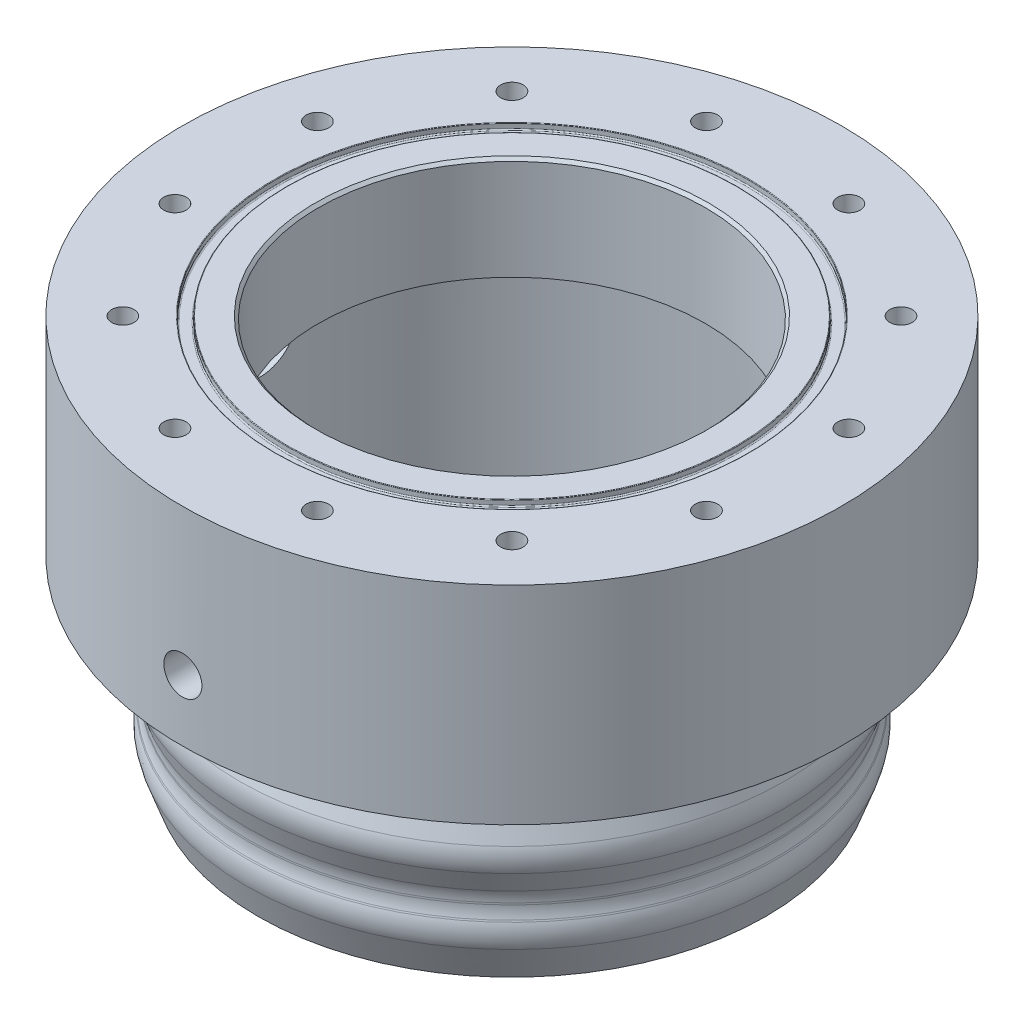
SolidWorks part; units mm, degrees
note: '?' marks a value the reader was unsure of.
material "7075-T6 (SN)"
ref_plane "Front Plane" through (0, 0, 0) normal (0, 0, 1) x (1, 0, 0)
ref_plane "Top Plane" through (0, 0, 0) normal (0, 1, 0) x (1, 0, 0)
ref_plane "Right Plane" through (0, 0, 0) normal (1, 0, 0) x (0, 0, -1)
sketch "Flange profile" plane through (0, 0, 0) normal (0, 0, 1) x (1, 0, 0)
  line L0 (0, 0) -> (0, 94.4875) construction
  line L1 (-42.8625, 22.86) -> (-42.8625, 0)
  line L2 (-73.025, 22.86) -> (-52.5653, 22.86)
  line L3 (-42.8625, 0) -> (-55.7276, 0)
  line L4 (-55.7276, 0) -> (-55.7276, -64.2669)
  line L5 (-42.8625, 22.86) -> (-49.7459, 22.86)
  line L6 (-52.4383, 22.733) -> (-52.4383, 21.7932)
  line L7 (-52.1843, 21.5392) -> (-50.1269, 21.5392)
  line L8 (-49.8729, 21.7932) -> (-49.8729, 22.733)
  line L9 (-73.025, 22.86) -> (-73.025, -23.1513)
  line L11 (-73.025, -23.1513) -> (-48.6828, -23.1513) construction
  line L16 (-58.2676, -47.2363) -> (-58.2676, -50.3097)
  line L17 (-73.025, -23.1513) -> (-58.2676, -23.1513)
  line L18 (-48.9204, -44.4628) -> (-48.9204, -68.3701) construction
  line L19 (-58.2676, -47.2363) -> (-61.3156, -38.862)
  line L20 (-61.3156, -38.862) -> (-58.2676, -30.4877)
  line L21 (-58.2676, -30.4877) -> (-58.2676, -23.1513)
  line L22 (-59.7916, -54.4969) -> (-56.2356, -64.2669)
  line L23 (-56.2356, -64.2669) -> (-55.7276, -64.2669)
  line L24 (-58.2676, -50.3097) -> (-59.7916, -54.4969)
  arc A0 (-49.8729, 21.7932) -> (-50.1269, 21.5392) centre (-50.1269, 21.7932) cw
  arc A1 (-52.1843, 21.5392) -> (-52.4383, 21.7932) centre (-52.1843, 21.7932) cw
  arc A2 (-49.7459, 22.86) -> (-49.8729, 22.733) centre (-49.7459, 22.733) ccw
  arc A3 (-52.4383, 22.733) -> (-52.5653, 22.86) centre (-52.5653, 22.733) ccw
  point P27 (-49.8729, 21.5392)
  point P32 (-49.8729, 22.86)
  point P35 (-52.4383, 22.86)
  dimension "D20" = 61.722
  dimension "D22" = 0.508
  dimension "D12" = 0.254
  dimension "D14" = 0.254
  dimension "D18" = 0.127
  dimension "D21" = 0.127
  dimension "D3" = 73.025
  dimension "D4" = 55.7276
  dimension "D5" = 4.064
  dimension "D6" = 52.4383
  dimension "D7" = 2.5654
  dimension "D8" = 1.3208
  dimension "D9" = 2.54
  dimension "D10" = 42.8625
  dimension "D11" = 20
  dimension "D13" = 2.54
  dimension "D15" = 20
  dimension "D16" = 46.0113
  dimension "D17" = 5.588
  dimension "D23" = 20
  dimension "D24" = 20
  dimension "D25" = 3.0734
revolve "Flange" add sketch "Flange profile" angle 360 about L0
ref_axis "center of part" through (0, 0, 0) along (0, -1, 0)?
ref_plane "Igniter Ref Plane" through (-71.0946, 0, 0) normal (1, 0, 0) x (0, 0, -1)
ref_plane "Assembly Bolt Offset Angle" through (0, 0, 0) normal (-0.2588, 0, 0.9659) x (0.9659, 0, 0.2588)
sketch "Assembly Bolt Insert Diameter" plane through (0, 22.86, 0) normal (0, 1, 0) x (1, 0, 0)
  line L0 (-70.4383, 18.8739) -> (70.4383, -18.8739) construction
  circle A0 centre (-58.8828, 15.7776) radius 2.4892
  dimension "D2" = 4.9784
  dimension "D1" = 60.96
extrude "Assembly Bolt Insert Cut" cut sketch "Assembly Bolt Insert Diameter" against normal blind 21.59
pattern_circular "Assembly Bolts" count 12 over 360 about axis through (0, 0, 0) along (0, 1, 0) of "Assembly Bolt Insert Cut"
sketch "Ref Line for Igniter Cut" plane through (0, 0, 0) normal (0, -1, 0) x (1, 0, 0)
  line L0 (-38.1, 0) -> (-38.1, 25.3157)
thread "Thread6" [suppressed] pitch 1.27 start angle 0, offset 0, length 20.32, pitch 1.27, diameter 4.9784
ref_plane "Plane9" through (-18.2668, 22.86, 58.8828) normal (0, 0, 1) x (-1, 0, 0)
sketch "Thread Profile7" plane through (-18.2668, 22.86, 58.8828) normal (0, 0, 1) x (-1, 0, 0)
  line L0 (0, 0) -> (0, 1.27) construction
  line L1 (0, 0) -> (0.6874, 0.3969)
  line L2 (0.6874, 0.3969) -> (0.6874, 0.5556)
  line L3 (0.6874, 0.5556) -> (0, 0.9525)
  line L4 (0.6874, 0.4762) -> (0, 0.4762) construction
  line L11 (0, 0) -> (0, 0.9525)
  point P2 (0, 0)
  dimension "Pitch" = 1.27
  dimension "Profile_Angle" = 60
  dimension "Profile_Land" = 0.1588
  dimension "Profile_Height" = 0.6874
ref_plane "Plane for Igniter Angle" through (-73.025, 0, 0) normal (-1, 0, 0) x (0, 0, 1)
sketch "Location and sizing of Igniter Cut and Boss" plane through (-73.025, 0, 0) normal (-1, 0, 0) x (0, 0, 1)
  line L5 (0, -55) -> (0, 55) construction
  circle A0 centre (0, 0) radius 8.7122
  dimension "D1" = 17.4244
ref_plane "Igniter Boss Plane" through (-81.3816, 0, 0) normal (1, 0, 0) x (0, 0, -1)
ref_plane "Plane for Pt Cut" through (0, 0, 50.8) normal (0, 0, 1) x (1, 0, 0)
sketch "Pt Cut Diameter" plane through (0, 0, 50.8) normal (0, 0, 1) x (1, 0, 0)
  circle A0 centre (0, -9.525) radius 4.2164
  dimension "D1" = 9.525
  dimension "D2" = 8.4328
extrude "Pt Cut" cut sketch "Pt Cut Diameter" along normal through all
ref_plane "Plane for PT Nipple Cut" through (57.912, 0, 0) normal (1, 0, 0) x (0, 0, -1)
ref_plane "Plane2" through (0, 0, 50.8) normal (0, 0, 1) x (1, 0, 0)
sketch "ref line for Interfence check: bolts and igniter port" plane through (0, 22.86, 0) normal (0, 1, 0) x (1, 0, 0)
  line L0 (-58.8828, 18.2668) -> (-58.8828, 13.2884)
  circle A0 centre (-58.8828, 15.7776) radius 2.4892 construction
ref_plane "Interference check: bolts and igniter port" through (-58.8828, 0, 0) normal (-1, 0, 0) x (0, 0, 1)
fillet "Fillet1" radius 7.62 1 edges at (0, -38.862, -61.3156)
fillet "Fillet2" radius 2.54 2 edges at (0, -23.1513, -58.2676) (0, 0, -55.7276)
fillet "Fillet3" radius 7.62 1 edges at (0, -54.4969, -59.7916)
fillet "Fillet7" radius 7.62 3 edges at (0, -50.3097, -58.2676) (0, -47.2363, -58.2676) (0, -30.4877, -58.2676)
sketch "Sketch24" plane through (-73.025, 0, 0) normal (-1, 0, 0) x (0, 0, 1)
  circle A0 centre (0, -9.525) radius 7.1438
  dimension "D1" = 14.2875
  dimension "D2" = 9.525
extrude "Cut-Extrude2" cut sketch "Sketch24" against normal blind 25.4
pattern_circular "CirPattern4" [suppressed] count 12 over 360
chamfer "Chamfer1" distance 0.635 angle 45 1 edges at (0, 22.86, -42.8625)
